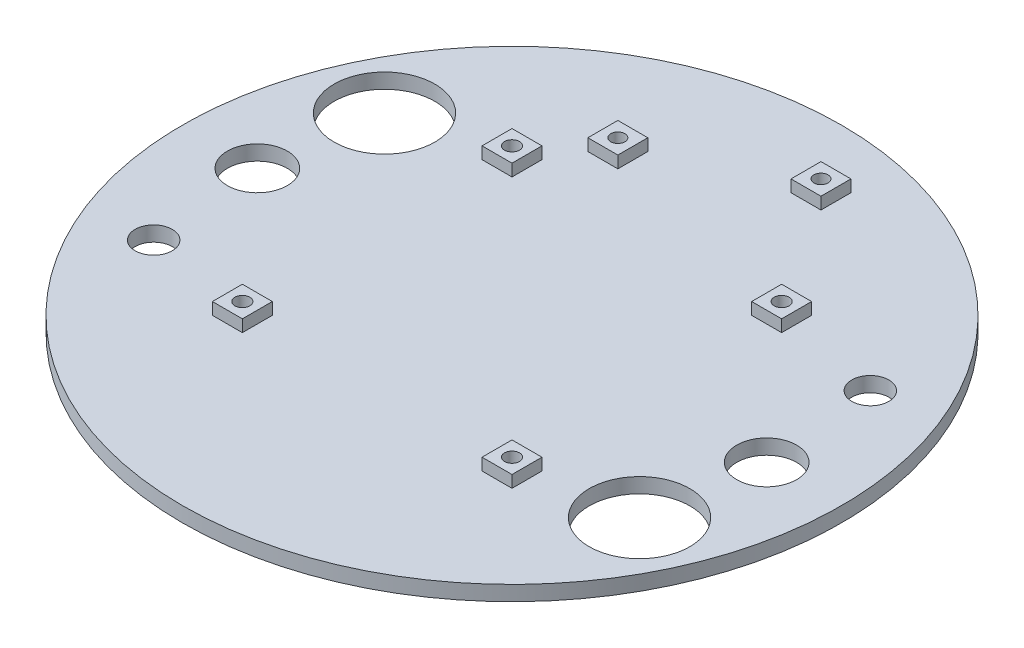
SolidWorks part; units mm, degrees
ref_plane "Front Plane" through (0, 0, 0) normal (0, 0, 1) x (1, 0, 0)
ref_plane "Top Plane" through (0, 0, 0) normal (0, 1, 0) x (1, 0, 0)
ref_plane "Right Plane" through (0, 0, 0) normal (1, 0, 0) x (0, 0, -1)
sketch "Sketch1" plane through (0, 0, 0) normal (0, 1, 0) x (1, 0, 0)
  line L0 (53.975, 0) -> (-53.975, 0) construction
  line L1 (0, 0) -> (-50.6445, 23.6159) construction
  line L2 (0, 0) -> (50.6445, -23.6159) construction
  line L3 (51.7955, 24.1526) -> (-51.7955, -24.1526) construction
  circle A0 centre (0, 0) radius 69.85
  circle A1 centre (-51.7955, -24.1526) radius 3.937
  circle A2 centre (-53.975, 0) radius 6.35
  circle A3 centre (-50.6445, 23.6159) radius 10.668
  circle A4 centre (51.7955, 24.1526) radius 3.937
  circle A5 centre (53.975, 0) radius 6.35
  circle A6 centre (50.6445, -23.6159) radius 10.668
  point P6 (0, 0)
  point P11 (0, 0)
extrude "Boss-Extrude1" add sketch "Sketch1" along normal blind 3.175
sketch "Sketch2" plane through (0, 3.175, 0) normal (0, 1, 0) x (1, 0, 0)
  line L0 (-28.575, -37.846) -> (-28.575, -28.575) construction
  line L1 (-37.846, -37.846) -> (37.846, -37.846) construction
  line L2 (-37.846, -37.846) -> (-37.846, 37.846) construction
  line L3 (-37.846, 37.846) -> (37.846, 37.846) construction
  line L4 (37.846, -37.846) -> (37.846, 37.846) construction
  line L5 (-37.846, -37.846) -> (37.846, 37.846) construction
  line L6 (-37.846, 37.846) -> (37.846, -37.846) construction
  line L7 (-37.846, 37.846) -> (-37.846, 28.575) construction
  line L8 (37.846, 37.846) -> (37.846, 28.575) construction
  line L9 (37.846, -37.846) -> (37.846, -28.575) construction
  line L10 (-37.846, -37.846) -> (-37.846, -28.575) construction
  line L11 (-37.846, -37.846) -> (-28.575, -37.846) construction
  line L12 (37.846, -37.846) -> (28.575, -37.846) construction
  line L13 (37.846, 37.846) -> (28.575, 37.846) construction
  line L14 (28.575, -37.846) -> (28.575, -28.575) construction
  line L15 (28.575, 37.846) -> (28.575, 28.575) construction
  line L16 (-37.846, 28.575) -> (-28.575, 28.575) construction
  line L18 (-25.4, 25.4) -> (-31.75, 25.4)
  line L19 (-25.4, 25.4) -> (-25.4, 31.75)
  line L20 (-25.4, 31.75) -> (-31.75, 31.75)
  line L21 (-31.75, 25.4) -> (-31.75, 31.75)
  line L22 (-25.4, 25.4) -> (-31.75, 31.75) construction
  line L23 (-25.4, 31.75) -> (-31.75, 25.4) construction
  line L24 (25.4, 25.4) -> (31.75, 25.4)
  line L25 (25.4, 25.4) -> (25.4, 31.75)
  line L26 (25.4, 31.75) -> (31.75, 31.75)
  line L27 (31.75, 25.4) -> (31.75, 31.75)
  line L28 (25.4, 25.4) -> (31.75, 31.75) construction
  line L29 (25.4, 31.75) -> (31.75, 25.4) construction
  line L30 (-31.75, -31.75) -> (-25.4, -31.75)
  line L31 (-31.75, -31.75) -> (-31.75, -25.4)
  line L32 (-31.75, -25.4) -> (-25.4, -25.4)
  line L33 (-25.4, -31.75) -> (-25.4, -25.4)
  line L34 (-31.75, -31.75) -> (-25.4, -25.4) construction
  line L35 (-31.75, -25.4) -> (-25.4, -31.75) construction
  line L36 (31.75, -31.75) -> (25.4, -31.75)
  line L37 (31.75, -31.75) -> (31.75, -25.4)
  line L38 (31.75, -25.4) -> (25.4, -25.4)
  line L39 (25.4, -31.75) -> (25.4, -25.4)
  line L40 (31.75, -31.75) -> (25.4, -25.4) construction
  line L41 (31.75, -25.4) -> (25.4, -31.75) construction
  circle A0 centre (-28.575, 28.575) radius 1.5875
  circle A1 centre (28.575, 28.575) radius 1.5875
  circle A2 centre (28.575, -28.575) radius 1.5875
  circle A4 centre (-28.575, -28.575) radius 1.5875
  point P0 (0, 0)
extrude "Cut-Extrude2" cut sketch "Sketch2" against normal blind 10 contours A4
extrude "Cut-Extrude3" cut sketch "Sketch2<4>" against normal blind 10 contours A0 | A1 | A2
sketch "Sketch2<4>" plane through (0, 3.175, 0) normal (0, 1, 0) x (1, 0, 0) same geometry as "Sketch2"
extrude "Boss-Extrude3" add sketch "Sketch2<5>" along normal blind 2.54
sketch "Sketch2<5>" plane through (0, 3.175, 0) normal (0, 1, 0) x (1, 0, 0) same geometry as "Sketch2"
sketch "Sketch4" plane through (0, 3.175, 0) normal (0, 1, 0) x (1, 0, 0)
  line L0 (-22.0222, 38.105) -> (-18.8472, 38.105) construction
  line L1 (22.9358, 38.105) -> (-22.0222, 38.105) construction
  line L2 (22.9358, 38.105) -> (22.9358, 58.425) construction
  line L3 (22.9358, 58.425) -> (-22.0222, 58.425) construction
  line L4 (-22.0222, 38.105) -> (-22.0222, 58.425) construction
  line L5 (22.9358, 38.105) -> (-22.0222, 58.425) construction
  line L6 (22.9358, 58.425) -> (-22.0222, 38.105) construction
  line L7 (-18.8472, 38.105) -> (-18.8472, 41.28) construction
  line L8 (22.9358, 58.425) -> (10.2358, 58.425) construction
  line L9 (10.2358, 58.425) -> (10.2358, 55.25) construction
  line L11 (-15.6722, 38.105) -> (-22.0222, 38.105)
  line L12 (-15.6722, 38.105) -> (-15.6722, 44.455)
  line L13 (-15.6722, 44.455) -> (-22.0222, 44.455)
  line L14 (-22.0222, 38.105) -> (-22.0222, 44.455)
  line L15 (-15.6722, 38.105) -> (-22.0222, 44.455) construction
  line L16 (-15.6722, 44.455) -> (-22.0222, 38.105) construction
  line L17 (13.4108, 52.075) -> (7.0608, 52.075)
  line L18 (13.4108, 52.075) -> (13.4108, 58.425)
  line L19 (13.4108, 58.425) -> (7.0608, 58.425)
  line L20 (7.0608, 52.075) -> (7.0608, 58.425)
  line L21 (13.4108, 52.075) -> (7.0608, 58.425) construction
  line L22 (13.4108, 58.425) -> (7.0608, 52.075) construction
  circle A1 centre (10.2358, 55.25) radius 1.5
  circle A2 centre (-18.8472, 41.28) radius 1.5
  point P0 (0.4568, 48.265)
extrude "Cut-Extrude4" cut sketch "Sketch4" against normal blind 6.35 contours A1 | A2
extrude "Boss-Extrude4" add sketch "Sketch4<4>" along normal blind 2.54
sketch "Sketch4<4>" plane through (0, 3.175, 0) normal (0, 1, 0) x (1, 0, 0) same geometry as "Sketch4"
